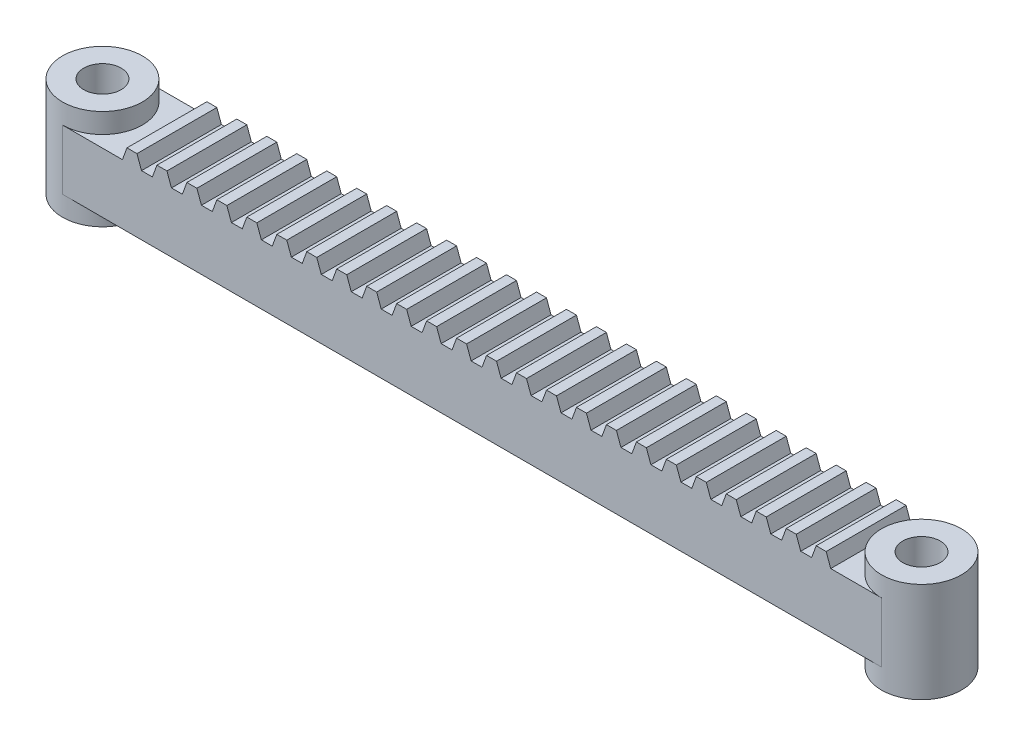
SolidWorks part; units mm, degrees
ref_plane "Front Plane" through (0, 0, 0) normal (0, 0, 1) x (1, 0, 0)
ref_plane "Top Plane" through (0, 0, 0) normal (0, 1, 0) x (1, 0, 0)
ref_plane "Right Plane" through (0, 0, 0) normal (1, 0, 0) x (0, 0, -1)
sketch "Sketch2" plane through (0, 0, 0) normal (0, 1, 0) x (1, 0, 0)
  line L0 (-55, 0) -> (55, 0) construction
  line L1 (82, -8) -> (-82, -8)
  line L3 (82, 8) -> (-82, 8)
  line L5 (82, -8) -> (-82, 8) construction
  line L6 (82, 8) -> (-82, -8) construction
  circle A0 centre (-82, 0) radius 8
  circle A1 centre (82, 0) radius 8
  circle A2 centre (-82, 0) radius 3.75
  circle A3 centre (82, 0) radius 3.75
  point P0 (0, 0)
  dimension "D4" = 16
  dimension "D5" = 7.5
  dimension "D6" = 7.5
  dimension "D1" = 164
  dimension "D2" = 16
  dimension "D3" = 16
extrude "Boss-Extrude1" add sketch "Sketch2" along normal mid plane 20 contours A0 A2 | A1 A3 region at (74.2263, 0, 0) region at (-89.7737, 0, 0)
extrude "Boss-Extrude2" add sketch "Sketch2<3>" along normal mid plane 12 contours A1 L3 A0 L1 region at (0, 0, 0)
sketch "Sketch2<3>" plane through (0, 0, 0) normal (0, 1, 0) x (1, 0, 0) same geometry as "Sketch2"
sketch "Sketch3" plane through (0, 0, 8) normal (0, 0, 1) x (1, 0, 0)
  line L1 (82, 6) -> (-82, 6) construction
  line L2 (-70, 6) -> (-69.0901, 8.5)
  line L3 (-69.0901, 8.5) -> (-67.0901, 8.5)
  line L4 (-67.0901, 8.5) -> (-66.1801, 6)
  line L5 (-68.0901, 8.5) -> (-68.0901, 6) construction
  line L9 (-66.1801, 6) -> (-64, 6)
  line L10 (-60.1801, 6) -> (-58, 6)
  line L11 (-61.0901, 8.5) -> (-60.1801, 6)
  line L12 (-63.0901, 8.5) -> (-61.0901, 8.5)
  line L13 (-64, 6) -> (-63.0901, 8.5)
  line L14 (-54.1801, 6) -> (-52, 6)
  line L15 (-55.0901, 8.5) -> (-54.1801, 6)
  line L16 (-57.0901, 8.5) -> (-55.0901, 8.5)
  line L17 (-58, 6) -> (-57.0901, 8.5)
  line L18 (-48.1801, 6) -> (-46, 6)
  line L19 (-49.0901, 8.5) -> (-48.1801, 6)
  line L20 (-51.0901, 8.5) -> (-49.0901, 8.5)
  line L21 (-52, 6) -> (-51.0901, 8.5)
  line L22 (-42.1801, 6) -> (-40, 6)
  line L23 (-43.0901, 8.5) -> (-42.1801, 6)
  line L24 (-45.0901, 8.5) -> (-43.0901, 8.5)
  line L25 (-46, 6) -> (-45.0901, 8.5)
  line L26 (-36.1801, 6) -> (-34, 6)
  line L27 (-37.0901, 8.5) -> (-36.1801, 6)
  line L28 (-39.0901, 8.5) -> (-37.0901, 8.5)
  line L29 (-40, 6) -> (-39.0901, 8.5)
  line L30 (-30.1801, 6) -> (-28, 6)
  line L31 (-31.0901, 8.5) -> (-30.1801, 6)
  line L32 (-33.0901, 8.5) -> (-31.0901, 8.5)
  line L33 (-34, 6) -> (-33.0901, 8.5)
  line L34 (-24.1801, 6) -> (-22, 6)
  line L35 (-25.0901, 8.5) -> (-24.1801, 6)
  line L36 (-27.0901, 8.5) -> (-25.0901, 8.5)
  line L37 (-28, 6) -> (-27.0901, 8.5)
  line L38 (-18.1801, 6) -> (-16, 6)
  line L39 (-19.0901, 8.5) -> (-18.1801, 6)
  line L40 (-21.0901, 8.5) -> (-19.0901, 8.5)
  line L41 (-22, 6) -> (-21.0901, 8.5)
  line L42 (-12.1801, 6) -> (-10, 6)
  line L43 (-13.0901, 8.5) -> (-12.1801, 6)
  line L44 (-15.0901, 8.5) -> (-13.0901, 8.5)
  line L45 (-16, 6) -> (-15.0901, 8.5)
  line L46 (-6.1801, 6) -> (-4, 6)
  line L47 (-7.0901, 8.5) -> (-6.1801, 6)
  line L48 (-9.0901, 8.5) -> (-7.0901, 8.5)
  line L49 (-10, 6) -> (-9.0901, 8.5)
  line L50 (-0.1801, 6) -> (2, 6)
  line L51 (-1.0901, 8.5) -> (-0.1801, 6)
  line L52 (-3.0901, 8.5) -> (-1.0901, 8.5)
  line L53 (-4, 6) -> (-3.0901, 8.5)
  line L54 (5.8199, 6) -> (8, 6)
  line L55 (4.9099, 8.5) -> (5.8199, 6)
  line L56 (2.9099, 8.5) -> (4.9099, 8.5)
  line L57 (2, 6) -> (2.9099, 8.5)
  line L58 (11.8199, 6) -> (14, 6)
  line L59 (10.9099, 8.5) -> (11.8199, 6)
  line L60 (8.9099, 8.5) -> (10.9099, 8.5)
  line L61 (8, 6) -> (8.9099, 8.5)
  line L62 (17.8199, 6) -> (20, 6)
  line L63 (16.9099, 8.5) -> (17.8199, 6)
  line L64 (14.9099, 8.5) -> (16.9099, 8.5)
  line L65 (14, 6) -> (14.9099, 8.5)
  line L66 (23.8199, 6) -> (26, 6)
  line L67 (22.9099, 8.5) -> (23.8199, 6)
  line L68 (20.9099, 8.5) -> (22.9099, 8.5)
  line L69 (20, 6) -> (20.9099, 8.5)
  line L70 (29.8199, 6) -> (32, 6)
  line L71 (28.9099, 8.5) -> (29.8199, 6)
  line L72 (26.9099, 8.5) -> (28.9099, 8.5)
  line L73 (26, 6) -> (26.9099, 8.5)
  line L74 (35.8199, 6) -> (38, 6)
  line L75 (34.9099, 8.5) -> (35.8199, 6)
  line L76 (32.9099, 8.5) -> (34.9099, 8.5)
  line L77 (32, 6) -> (32.9099, 8.5)
  line L78 (41.8199, 6) -> (44, 6)
  line L79 (40.9099, 8.5) -> (41.8199, 6)
  line L80 (38.9099, 8.5) -> (40.9099, 8.5)
  line L81 (38, 6) -> (38.9099, 8.5)
  line L82 (47.8199, 6) -> (50, 6)
  line L83 (46.9099, 8.5) -> (47.8199, 6)
  line L84 (44.9099, 8.5) -> (46.9099, 8.5)
  line L85 (44, 6) -> (44.9099, 8.5)
  line L86 (53.8199, 6) -> (56, 6)
  line L87 (52.9099, 8.5) -> (53.8199, 6)
  line L88 (50.9099, 8.5) -> (52.9099, 8.5)
  line L89 (50, 6) -> (50.9099, 8.5)
  line L90 (59.8199, 6) -> (62, 6)
  line L91 (58.9099, 8.5) -> (59.8199, 6)
  line L92 (56.9099, 8.5) -> (58.9099, 8.5)
  line L93 (56, 6) -> (56.9099, 8.5)
  line L94 (65.8199, 6) -> (68, 6)
  line L95 (64.9099, 8.5) -> (65.8199, 6)
  line L96 (62.9099, 8.5) -> (64.9099, 8.5)
  line L97 (62, 6) -> (62.9099, 8.5)
  line L98 (71.8199, 6) -> (74, 6)
  line L99 (70.9099, 8.5) -> (71.8199, 6)
  line L100 (68.9099, 8.5) -> (70.9099, 8.5)
  line L101 (68, 6) -> (68.9099, 8.5)
  line L103 (-70, 6) -> (-72.9783, 6)
  line L104 (-72.9783, 6) -> (-72.9783, 3.3965)
  line L105 (-72.9783, 3.3965) -> (74, 3.3965)
  line L106 (74, 3.3965) -> (74, 6)
  dimension "D1" = 2
  dimension "D2" = 2.5
  dimension "D3" = 6
  dimension "D4" = 40
  dimension "D5" = 20
  dimension "D6" = 20
  dimension "D8" = 146.9783
  dimension "D9" = 2.6035
  dimension "D7" = 24
extrude "Boss-Extrude3" add sketch "Sketch3" against normal blind 16
